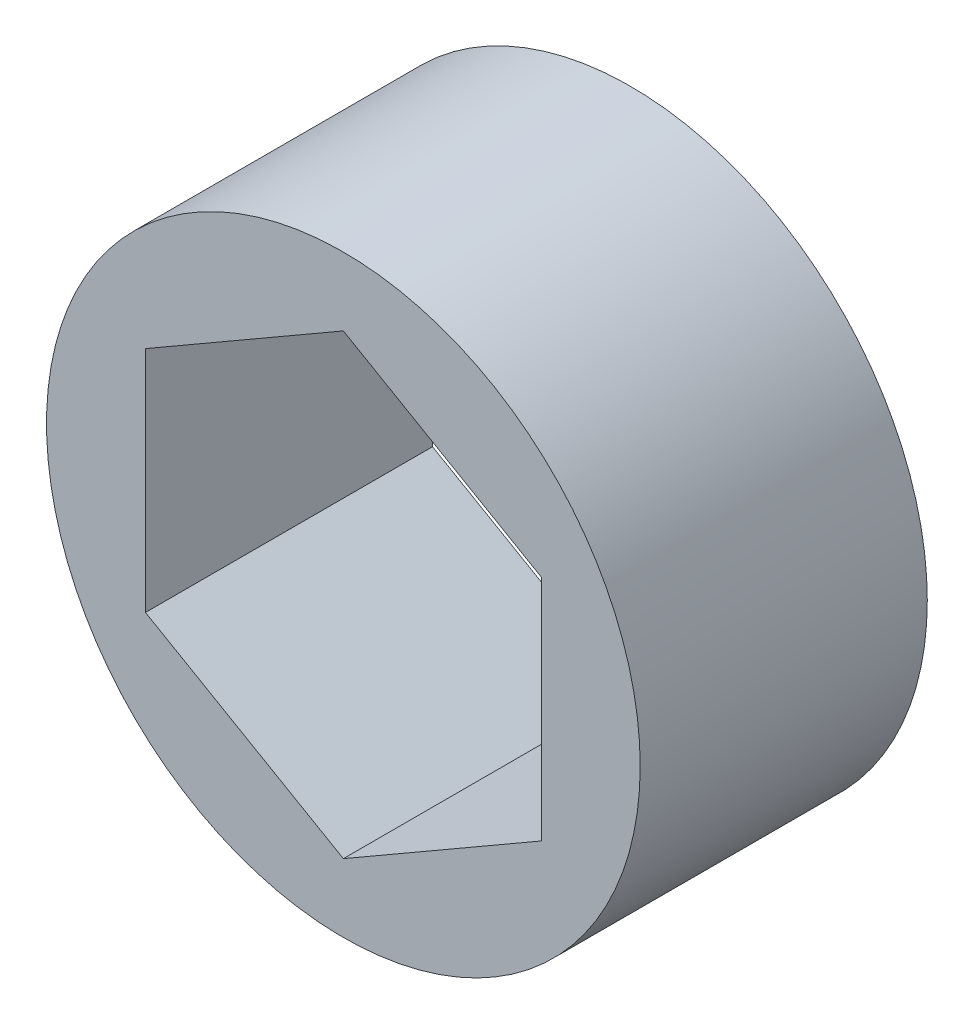
SolidWorks part; units mm, degrees
material "PET"
ref_plane "Front Plane" through (0, 0, 0) normal (0, 0, 1) x (1, 0, 0)
ref_plane "Top Plane" through (0, 0, 0) normal (0, 1, 0) x (1, 0, 0)
ref_plane "Right Plane" through (0, 0, 0) normal (1, 0, 0) x (0, 0, -1)
sketch "Sketch1" plane through (0, 0, 0) normal (0, 0, 1) x (1, 0, 0)
  line L1 (0, 7.3323) -> (-6.35, 3.6662)
  line L2 (-6.35, 3.6662) -> (-6.35, -3.6662)
  line L3 (-6.35, -3.6662) -> (0, -7.3323)
  line L4 (0, -7.3323) -> (6.35, -3.6662)
  line L5 (6.35, -3.6662) -> (6.35, 3.6662)
  line L6 (6.35, 3.6662) -> (0, 7.3323)
  circle A0 centre (0, 0) radius 6.35 construction
  circle A1 centre (0, 0) radius 9.525
  dimension "D1" = 19.05
  dimension "D2" = 12.7
extrude "Boss-Extrude1" add sketch "Sketch1" along normal mid plane 9.2121
